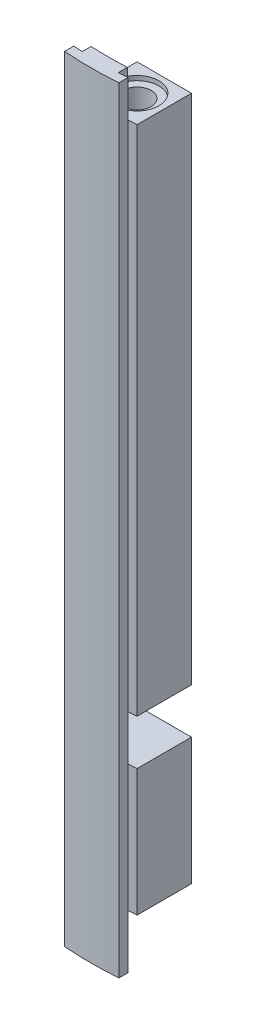
SolidWorks part; units mm, degrees
ref_plane "Front Plane" through (0, 0, 0) normal (0, 0, 1) x (1, 0, 0)
ref_plane "Top Plane" through (0, 0, 0) normal (0, 1, 0) x (1, 0, 0)
ref_plane "Right Plane" through (0, 0, 0) normal (1, 0, 0) x (0, 0, -1)
ref_plane "Plane7" through (0, -5, 0) normal (0, -1, 0) x (-1, 0, 0)
sketch "Sketch1" plane through (0, 0, 0) normal (0, 1, 0) x (1, 0, 0)
  circle A0 centre (0, 0) radius 37.5 construction
  dimension "D1" = 75
sketch "Sketch3" plane through (0, -5, 0) normal (0, -1, 0) x (1, 0, 0)
  line L0 (-3, 37.3798) -> (-3, 31.3798)
  line L1 (-3, 31.3798) -> (3, 31.3798)
  line L2 (3, 31.3798) -> (3, 37.3798)
  line L9 (0, 40.3758) -> (0, -39.6162) construction
  line L10 (0, -41.25) -> (0, 41.25) construction
  arc A0 (3, 37.3798) -> (-3, 37.3798) centre (0, 0) ccw
  circle A4 centre (0, 0) radius 37.5 construction
  dimension "D2" = 6
  dimension "D3" = 6
extrude "Boss-Extrude2" add sketch "Sketch3" along normal blind 75.5
sketch "Sketch5" plane through (0, 0, 0) normal (0, 1, 0) x (1, 0, 0)
  line L0 (-3, -38.3602) -> (-3, -39.3859)
  line L1 (3, -38.381) -> (3, -39.3859)
  line L2 (2, -38.4461) -> (2, -37.4466)
  line L3 (-2, -38.4253) -> (-2, -37.4466)
  line L12 (0, 40.7328) -> (0, -41.0085) construction
  line L13 (0, -41.25) -> (0, 41.25) construction
  arc A0 (-3, -39.3859) -> (3, -39.3859) centre (0, 0) ccw
  arc A1 (-2, -37.4466) -> (2, -37.4466) centre (0, 0) ccw
  arc A2 (3, -38.381) -> (2, -38.4461) centre (0, 0) cw
  arc A3 (-3, -38.3602) -> (-2, -38.4253) centre (0, 0) ccw
  circle A13 centre (0, 0) radius 37.5 construction
  dimension "D2" = 6
  dimension "D3" = 2
  dimension "D4" = 1.0049
  dimension "D5" = 1
extrude "Boss-Extrude3" add sketch "Sketch5" against normal blind 85.5
sketch "Sketch7" plane through (0, 0, 0) normal (1, 0, 0) x (0, 0, -1)
  line L0 (0, 41.25) -> (0, -41.25) construction
  line L1 (0, -61.5) -> (-37.5, -61.5)
  line L2 (0, -61.5) -> (0, -66.5)
  line L3 (0, -66.5) -> (-37.5, -66.5)
  line L4 (-37.5, -61.5) -> (-37.5, -66.5)
  line L6 (-31.3798, -80.5) -> (-37.3798, -80.5) construction
  line L7 (0, -27.0167) -> (0, -72.0117) construction
  dimension "D1" = 37.5
  dimension "D2" = 5
  dimension "D3" = 14
revolve "Cut-Revolve1" cut sketch "Sketch7" angle 360 about L7
ref_plane "Plane5" through (0, -80.5, 0) normal (0, -1, 0) x (-1, 0, 0)
sketch "Sketch9" plane through (0, -80.5, 0) normal (0, -1, 0) x (-1, 0, 0)
  line L0 (0, -31.1751) -> (0, -37.6667) construction
  line L1 (0, 42.35) -> (0, -42.35) construction
  line L2 (-3.1738, -34.4209) -> (3.1592, -34.4209) construction
  circle A0 centre (0, -34.4209) radius 1.55
  dimension "D2" = 3.1
extrude "Cut-Extrude4" cut sketch "Sketch9" against normal blind 4.3
sketch "Sketch10" plane through (0, -80.5, 0) normal (0, -1, 0) x (-1, 0, 0)
  line L0 (0, -31.1751) -> (0, -37.6667) construction
  line L2 (-3.1738, -34.4209) -> (3.1592, -34.4209) construction
  circle A0 centre (0, -34.4209) radius 2.4
  dimension "D2" = 4.8
extrude "Cut-Extrude5" cut sketch "Sketch10" against normal blind 0.5
sketch "Sketch12" plane through (0, -5, 0) normal (0, -1, 0) x (-1, 0, 0)
  circle A0 centre (0, 0) radius 37.5 construction
sketch "Sketch13" plane through (0, -5, 0) normal (0, -1, 0) x (-1, 0, 0)
  line L0 (0, -31.134) -> (0, -37.6256) construction
  line L1 (-2.6479, -34.3798) -> (2.8747, -34.3798) construction
  line L2 (3, -37.3798) -> (3, -31.3798) construction
  line L3 (-3, -31.3798) -> (-3, -37.3798) construction
  circle A0 centre (0, -34.3798) radius 2.4
sketch "Sketch14" plane through (0, -5, 0) normal (0, -1, 0) x (-1, 0, 0)
  line L0 (0, -31.134) -> (0, -37.6256) construction
  line L2 (-3.1738, -34.3798) -> (3.1592, -34.3798) construction
  line L3 (3, -37.3798) -> (3, -31.3798) construction
  line L4 (-3, -31.3798) -> (-3, -37.3798) construction
  circle A0 centre (0, -34.3798) radius 1.55
  dimension "D2" = 3.1
extrude "Cut-Extrude6" cut sketch "Sketch13" along normal blind 0.5
extrude "Cut-Extrude7" cut sketch "Sketch14" along normal blind 4.3
